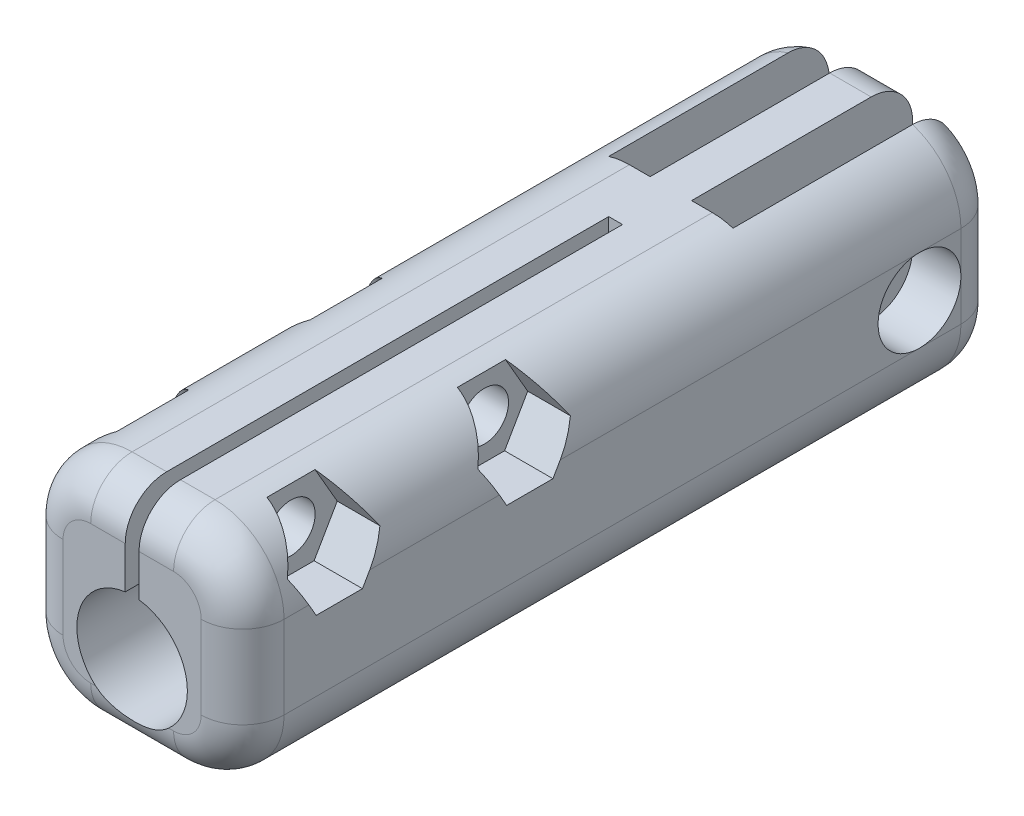
SolidWorks part; units mm, degrees
ref_plane "Front Plane" through (0, 0, 0) normal (0, 0, 1) x (1, 0, 0)
ref_plane "Top Plane" through (0, 0, 0) normal (0, 1, 0) x (1, 0, 0)
ref_plane "Right Plane" through (0, 0, 0) normal (1, 0, 0) x (0, 0, -1)
sketch "Sketch1" plane through (0, 0, 0) normal (0, 0, 1) x (1, 0, 0)
  line L1 (-8, -8) -> (8, -8)
  line L2 (-8, -8) -> (-8, 8)
  line L3 (-8, 8) -> (8, 8)
  line L4 (8, -8) -> (8, 8)
  line L5 (-8, -8) -> (8, 8) construction
  line L6 (-8, 8) -> (8, -8) construction
  point P0 (0, 0)
  dimension "D1" = 16
  dimension "D2" = 16
extrude "Boss-Extrude1" add sketch "Sketch1" along normal blind 55
sketch "Sketch2" plane through (0, 8, 0) normal (0, 1, 0) x (1, 0, 0)
  line L0 (0, 0) -> (0, -55) construction
  line L1 (8, 0) -> (-8, 0) construction
  line L2 (8, -55) -> (-8, -55) construction
  line L3 (-4.5, 0) -> (-1.5, -16) construction
  line L4 (1.5, -16) -> (-1.5, -16)
  line L5 (1.5, -16) -> (1.5, 0)
  line L6 (1.5, 0) -> (-1.5, 0)
  line L7 (-1.5, -16) -> (-1.5, 0)
  line L8 (1.5, -16) -> (-1.5, 0) construction
  line L9 (1.5, 0) -> (-1.5, -16) construction
  line L10 (4.5, -16) -> (1.5, -16)
  line L11 (4.5, -16) -> (4.5, 0)
  line L12 (4.5, 0) -> (1.5, 0)
  line L13 (1.5, -16) -> (1.5, 0)
  line L14 (4.5, -16) -> (1.5, 0) construction
  line L15 (4.5, 0) -> (1.5, -16) construction
  line L16 (-4.5, -16) -> (-4.5, 0)
  line L17 (-4.5, -16) -> (-1.5, -16)
  point P6 (0, -8)
  point P11 (3, -8)
  point P18 (-3, -8)
  line M7 (8, 0) -> (-8, 0)
  dimension "D1" = 3
  dimension "D2" = 16
extrude "Cut-Extrude1" cut sketch "Sketch2" against normal blind 45 contours L10 L11 L5 M7 | L16 L17 L7 M7 region at (3, 8, 8) region at (-3, 8, 8)
sketch "Sketch3" plane through (8, 0, 0) normal (1, 0, 0) x (0, 0, -1)
  line L0 (0, -8) -> (0, 8) construction
  circle A0 centre (-6, 0) radius 3
  dimension "D1" = 6
  dimension "D2" = 6
extrude "Cut-Extrude2" cut sketch "Sketch3" against normal blind 45
sketch "Sketch4" plane through (0, 0, 55) normal (0, 0, 1) x (1, 0, 0)
  line L0 (8, 8) -> (-8, 8) construction
  line L1 (0.5, 0.4246) -> (-0.5, 0.4246)
  line L2 (0.5, 0.4246) -> (0.5, 8)
  line L3 (0.5, 8) -> (-0.5, 8)
  line L4 (-0.5, 0.4246) -> (-0.5, 8)
  line L5 (0.5, 0.4246) -> (-0.5, 8) construction
  line L6 (0.5, 8) -> (-0.5, 0.4246) construction
  line L7 (-8, -8) -> (8, -8) construction
  line L8 (0, 8) -> (0, -8) construction
  circle A0 centre (0, -2) radius 4
  point P3 (0, 4.2123)
  point P10 (0.5, 0.4246)
  line M3 (8, 8) -> (-8, 8)
  dimension "D1" = 8
  dimension "D2" = 1
  dimension "D3" = 6
extrude "Cut-Extrude3" cut sketch "Sketch4" against normal blind 35 contours L4 A0 L2 L1 | A0 L2 L4 M3 | L2 A0 L4 L1 region at (0, -2.1031, 55) region at (0, 1.2071, 55) region at (0, 4.9948, 55)
fillet "Fillet1" radius 5 4 edges at (8, 8, 27.5) (-8, 8, 27.5) (8, -8, 27.5) (-8, -8, 27.5)
fillet "Fillet2" radius 3 17 edges at (7.0311, -5.958, 0) (8, 0, 0) (-7.0311, -5.958, 0) (-8, 0, 0) (-1.75, 8, 55) (1.75, 8, 55) (6.5355, 6.5355, 55) (8, 0, 55) (6.5355, -6.5355, 55) (0, -8, 55) (-6.5355, -6.5355, 55) (-8, 0, 55) (0, -8, 0) (7.0311, 5.958, 0) (0, 8, 0) (-7.0311, 5.958, 0) (-6.5355, 6.5355, 55)
sketch "Sketch5" plane through (0.5, 0, 0) normal (-1, 0, 0) x (0, 0, 1)
  line L0 (52, 8) -> (52, 1.9686) construction
  line L1 (20, 1.9686) -> (55, 1.9686) construction
  line L2 (52, 4.9843) -> (20, 4.9843) construction
  line L3 (20, 1.9686) -> (20, 8) construction
  circle A0 centre (48, 4.9843) radius 1.75
  circle A1 centre (34, 4.9843) radius 1.75
  point P13 (31.267, 4.9843)
  dimension "D1" = 3.5
  dimension "D2" = 3.5
  dimension "D3" = 4
  dimension "D4" = 14
extrude "Cut-Extrude4" cut sketch "Sketch5" against normal blind 40 and the other way blind 40 contours A0 | A1 region at (0.5, 4.9843, 48)
sketch "Sketch6" plane through (0.5, 0, 0) normal (-1, 0, 0) x (0, 0, 1)
  line L0 (20, 8) -> (52, 8) construction
  line L1 (49.6743, 7.8843) -> (46.3257, 7.8843)
  line L2 (46.3257, 7.8843) -> (44.6514, 4.9843)
  line L3 (44.6514, 4.9843) -> (46.3257, 2.0843)
  line L4 (46.3257, 2.0843) -> (49.6743, 2.0843)
  line L5 (49.6743, 2.0843) -> (51.3486, 4.9843)
  line L6 (51.3486, 4.9843) -> (49.6743, 7.8843)
  line L7 (35.8851, 7.8843) -> (32.5365, 7.8843)
  line L8 (32.5365, 7.8843) -> (30.8621, 4.9843)
  line L9 (30.8621, 4.9843) -> (32.5365, 2.0843)
  line L10 (32.5365, 2.0843) -> (35.8851, 2.0843)
  line L11 (35.8851, 2.0843) -> (37.5594, 4.9843)
  line L12 (37.5594, 4.9843) -> (35.8851, 7.8843)
  circle A0 centre (48, 4.9843) radius 2.9 construction
  circle A1 centre (34.2108, 4.9843) radius 2.9 construction
  dimension "D1" = 5.8
  dimension "D2" = 5.8
extrude "Cut-Extrude5" cut sketch "Sketch6" against normal blind 40 from offset 4 offset against normal yes
sketch "Sketch7" plane through (-0.5, 0, 0) normal (1, 0, 0) x (0, 0, -1)
  circle A0 centre (-48, 4.9843) radius 3.5
  circle A1 centre (-34, 4.9843) radius 3.5
extrude "Cut-Extrude6" cut sketch "Sketch7" against normal blind 40 from offset 5 offset against normal yes
